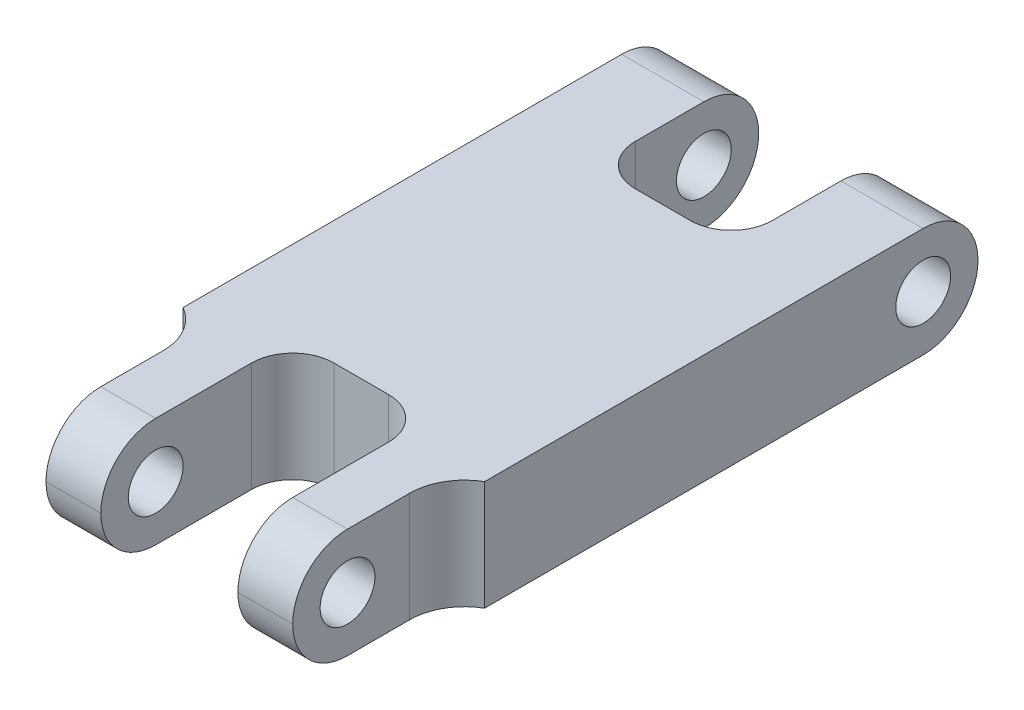
SolidWorks part; units mm, degrees
material "6061-T4 (SS)"
ref_plane "Front Plane" through (0, 0, 0) normal (0, 0, 1) x (1, 0, 0)
ref_plane "Top Plane" through (0, 0, 0) normal (0, 1, 0) x (1, 0, 0)
ref_plane "Right Plane" through (0, 0, 0) normal (1, 0, 0) x (0, 0, -1)
sketch "Sketch4" plane through (0, 0, 0) normal (0, 0, 1) x (1, 0, 0)
  line L1 (-17.4625, 6.35) -> (17.4625, 6.35)
  line L2 (-17.4625, 6.35) -> (-17.4625, -6.35)
  line L3 (-17.4625, -6.35) -> (17.4625, -6.35)
  line L4 (17.4625, 6.35) -> (17.4625, -6.35)
  dimension "D1" = 34.925
  dimension "D2" = 12.7
  dimension "D3" = 17.4625
  dimension "D4" = 6.35
extrude "Boss-Extrude2" add sketch "Sketch4" along normal blind 76.2
sketch "Sketch6" plane through (0, 6.35, 0) normal (0, 1, 0) x (1, 0, 0)
  line L0 (17.4625, -76.2) -> (-17.4625, -76.2) construction
  line L3 (-7.9375, -53.975) -> (7.9375, -53.975)
  line L4 (-7.9375, -53.975) -> (-7.9375, -76.2)
  line L5 (-7.9375, -76.2) -> (7.9375, -76.2)
  line L6 (7.9375, -53.975) -> (7.9375, -76.2)
  line L15 (17.4625, 0) -> (-17.4625, 0) construction
  line L16 (-7.9375, 0) -> (7.9375, 0)
  line L17 (-7.9375, 0) -> (-7.9375, -19.05)
  line L18 (-7.9375, -19.05) -> (7.9375, -19.05)
  line L19 (7.9375, 0) -> (7.9375, -19.05)
  point P6 (0, -53.975)
  point P23 (0, 0)
  dimension "D1" = 15.875
  dimension "D2" = 19.05
  dimension "D3" = 22.225
  dimension "D4" = 15.875
extrude "Cut-Extrude4" cut sketch "Sketch6" against normal through all
fillet "Fillet3" radius 6.35 8 edges at (-12.7, -6.35, 0) (12.7, -6.35, 0) (-12.7, 6.35, 0) (12.7, 6.35, 0) (12.7, -6.35, 76.2) (12.7, 6.35, 76.2) (-12.7, -6.35, 76.2) (-12.7, 6.35, 76.2)
sketch "Sketch7" plane through (17.4625, 0, 0) normal (1, 0, 0) x (0, 0, -1)
  line L1 (-69.85, 6.35) -> (-6.35, 6.35) construction
  line L2 (-69.85, -6.35) -> (-6.35, -6.35) construction
  circle A0 centre (-6.35, 0) radius 3.175
  circle A1 centre (-69.85, 0) radius 3.175
  dimension "D1" = 6.35
  dimension "D2" = 6.35
  dimension "D6" = 6.35
  dimension "D5" = 6.35
  dimension "D3" = 6.35
  dimension "D4" = 6.35
extrude "Cut-Extrude5" cut sketch "Sketch7" against normal through all
fillet "Fillet4" radius 4.7625 2 edges at (-7.9375, 0, 19.05) (7.9375, 0, 19.05)
fillet "Fillet5" radius 4.7625 2 edges at (7.9375, 0, 53.975) (-7.9375, 0, 53.975)
sketch "Sketch8" plane through (0, 6.35, 0) normal (0, 1, 0) x (1, 0, 0)
  line L1 (14.2875, -57.15) -> (17.4625, -57.15)
  line L2 (14.2875, -57.15) -> (14.2875, -76.2)
  line L3 (14.2875, -76.2) -> (17.4625, -76.2)
  line L4 (17.4625, -57.15) -> (17.4625, -76.2)
  line L5 (17.4625, -69.85) -> (17.4625, -6.35) construction
  line L7 (-14.2875, -57.15) -> (-17.4625, -57.15)
  line L8 (-14.2875, -57.15) -> (-14.2875, -76.2)
  line L9 (-14.2875, -76.2) -> (-17.4625, -76.2)
  line L10 (-17.4625, -57.15) -> (-17.4625, -76.2)
  dimension "D1" = 3.175
  dimension "D2" = 3.175
  dimension "D3" = 19.05
  dimension "D4" = 19.05
extrude "Cut-Extrude6" cut sketch "Sketch8" against normal through all
fillet "Fillet6" radius 6.35 2 edges at (-14.2875, 0, 57.15) (14.2875, 0, 57.15)
